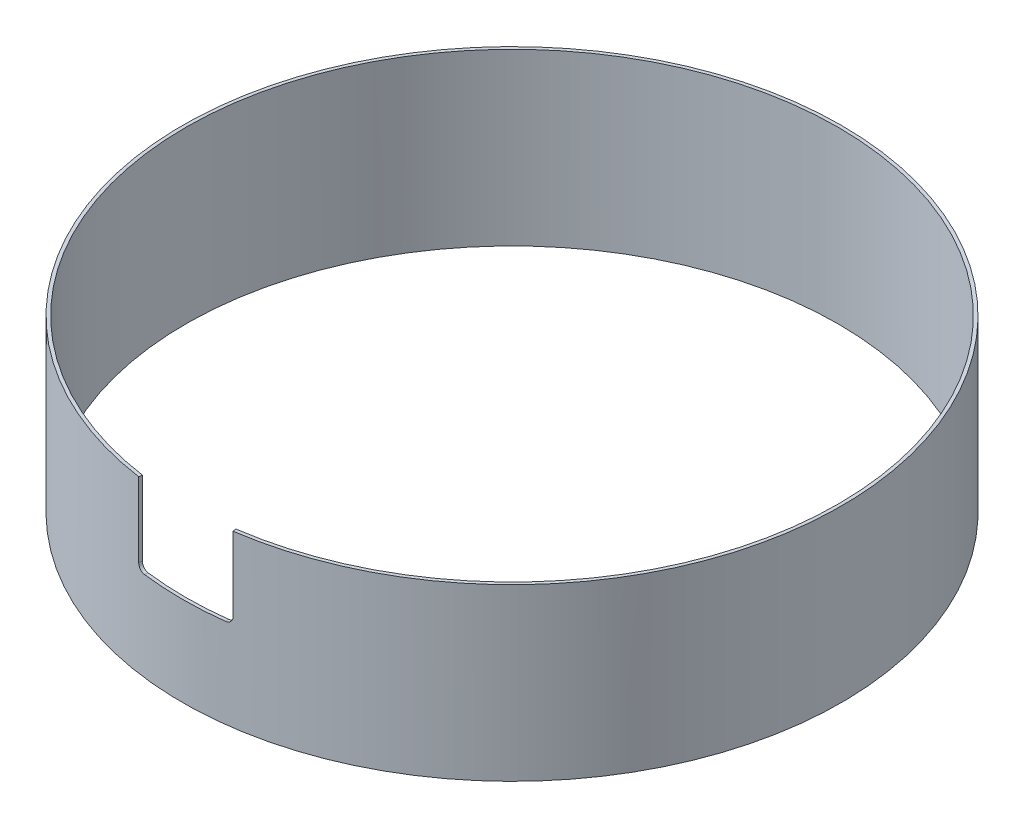
SolidWorks part; units mm, degrees
ref_plane "Front Plane" through (0, 0, 0) normal (0, 0, 1) x (1, 0, 0)
ref_plane "Top Plane" through (0, 0, 0) normal (0, 1, 0) x (1, 0, 0)
ref_plane "Right Plane" through (0, 0, 0) normal (1, 0, 0) x (0, 0, -1)
sketch "Эскиз1" plane through (0, 0, 0) normal (0, 1, 0) x (1, 0, 0)
  circle A0 centre (0, 0) radius 50.3
  circle A1 centre (0, 0) radius 49.8
extrude "Бобышка-Вытянуть1" add sketch "Эскиз1" along normal blind 24
sketch "Эскиз3" plane through (0, 24, 0) normal (0, 1, 0) x (1, 0, 0)
  line L6 (0, -50.3) -> (0, -52.1233) construction
  line L10 (0, -52.1233) -> (7.2, -52.1233) construction
  line L12 (-7.2, -52.1233) -> (0, -52.1233) construction
  line L13 (-7.1284, -49.2872) -> (-7.1993, -49.777)
  line L15 (-7.1993, -49.777) -> (-7.2, -49.782)
  line L16 (7.1993, -49.777) -> (7.2, -49.782)
  line L17 (7.1284, -49.2872) -> (7.1993, -49.777)
  circle A15 centre (0, 0) radius 49.8 construction
  arc A16 (-7.1284, -49.2872) -> (7.1284, -49.2872) centre (0, 0) ccw
  circle A17 centre (0, 0) radius 50.3 construction
  arc A18 (-7.2, -49.782) -> (7.2, -49.782) centre (0, 0) ccw
extrude "Вырез-Вытянуть2" cut sketch "Эскиз3" against normal blind 12.35
fillet "Скругление3" radius 1 2 edges at (7.1642, 11.65, 49.5346) (-7.1642, 11.65, 49.5346)
sketch "Эскиз4" plane through (0, 0, 0) normal (0, -1, 0) x (1, 0, 0)
  circle A0 centre (0, 0) radius 49.8 construction
  circle A1 centre (0, 0) radius 49.8
  circle A2 centre (0, 0) radius 50.3 construction
  circle A3 centre (0, 0) radius 50.3
extrude "Бобышка-Вытянуть2" add sketch "Эскиз4" along normal blind 2
